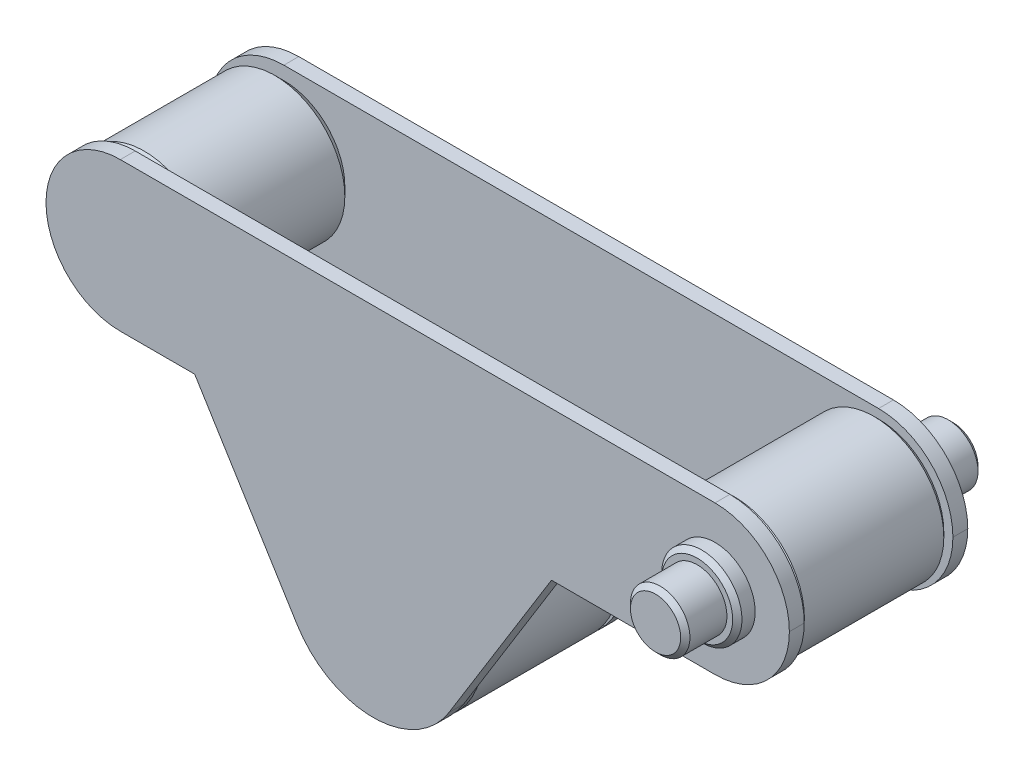
SolidWorks part; units mm, degrees
material "Сталь 3 ГОСТ 535-88"
ref_plane "Спереди" through (0, 0, 0) normal (0, 0, 1) x (1, 0, 0)
ref_plane "Сверху" through (0, 0, 0) normal (0, 1, 0) x (1, 0, 0)
ref_plane "Справа" through (0, 0, 0) normal (1, 0, 0) x (0, 0, -1)
sketch "Эскиз1" plane through (0, 0, 0) normal (1, 0, 0) x (0, 0, -1)
  line L1 (-50, 0) -> (-50, 10)
  line L2 (-50, 10) -> (-36, 10)
  line L3 (-36, 10) -> (-36, 13.5)
  line L4 (-36, 13.5) -> (-25, 13.5)
  line L5 (36, 13.5) -> (36, 10)
  line L6 (36, 10) -> (50, 10)
  line L7 (50, 10) -> (50, 0)
  line L8 (0, 25.8106) -> (0, -23.114) construction
  line L9 (-71.1264, 0) -> (85.8599, 0) construction
  line L10 (-50, 0) -> (50, 0)
  line L11 (25, 13.5) -> (36, 13.5)
  line L13 (25, 13.5) -> (25, 23.5)
  line L14 (25, 23.5) -> (-25, 23.5)
  line L15 (-25, 13.5) -> (-25, 23.5)
  point P12 (50, 5)
  dimension "D1" = 20
  dimension "D2" = 27
  dimension "D3" = 100
  dimension "D4" = 72
  dimension "D5" = 10
  dimension "D6" = 50
revolve "Повернуть1" add sketch "Эскиз1" angle 360 about L9
chamfer "Фаска1" distance 1.56 angle 45 6 edges at (10, 0, 50) (13.5, 0, 36) (10, 0, -50) (23.5, 0, 25) (23.5, 0, -25) (13.5, 0, -36)
sketch "Эскиз2" plane through (0, 0, -25) normal (0, 0, -1) x (-1, 0, 0)
  line L0 (-25, -25) -> (-25, 25)
  line L1 (-25, 25) -> (225, 25)
  line L2 (-25, -25) -> (55, -25)
  line L3 (55, -25) -> (89.4828, -80.7757)
  line L5 (140.5172, -80.7757) -> (175, -25)
  line L6 (175, -25) -> (225, -25)
  line L7 (225, -25) -> (225, 25)
  line L8 (-40.7297, 0) -> (66.8826, 0) construction
  line L9 (115, -95) -> (115, 11.3994) construction
  circle A0 centre (0, 0) radius 13.5 construction
  circle A1 centre (0, 0) radius 13.5
  arc A2 (89.4828, -80.7757) -> (140.5172, -80.7757) centre (115, -65) ccw
  dimension "D6" = 120
  dimension "D4" = 30
  dimension "D1" = 50
  dimension "D2" = 25
  dimension "D3" = 250
  dimension "D5" = 50
  dimension "D7" = 80
extrude "Бобышка-Вытянуть1" add sketch "Эскиз2" along normal blind 5 separate body
fillet "Скругление1" radius 25 4 edges at (25, -25, -27.5) (25, 25, -27.5) (-225, -25, -27.5) (-225, 25, -27.5)
mirror "Зеркальное отражение1" about plane through (0, 0, 0) normal (0, 0, 1) of bodies 104
sketch "Эскиз3" plane through (0, 0, -25) normal (0, 0, 1) x (1, 0, 0)
  arc A1 (-140.5172, -80.7757) -> (-89.4828, -80.7757) centre (-115, -65) ccw construction
  circle A2 centre (-115, -65) radius 30
extrude "Бобышка-Вытянуть2" add sketch "Эскиз3" along normal up to surface (50 mm away) separate body up to face at (-106, -22.5776, 25)
sketch "Эскиз4" plane through (0, 0, -25) normal (0, 0, 1) x (1, 0, 0)
  circle A0 centre (-200, 0) radius 23.5
  arc A1 (-200, 25) -> (-225, 0) centre (-200, 0) ccw construction
  dimension "D1" = 47
extrude "Бобышка-Вытянуть3" add sketch "Эскиз4" along normal up to surface (50 mm away) separate body up to face at (-106, -22.5776, 25)
chamfer "Фаска2" distance 3 angle 45 2 edges at (-176.5, 0, 25) (-176.5, 0, -25)
chamfer "Фаска3" distance 2 angle 45 2 edges at (-85, -65, 25) (-85, -65, -25)
